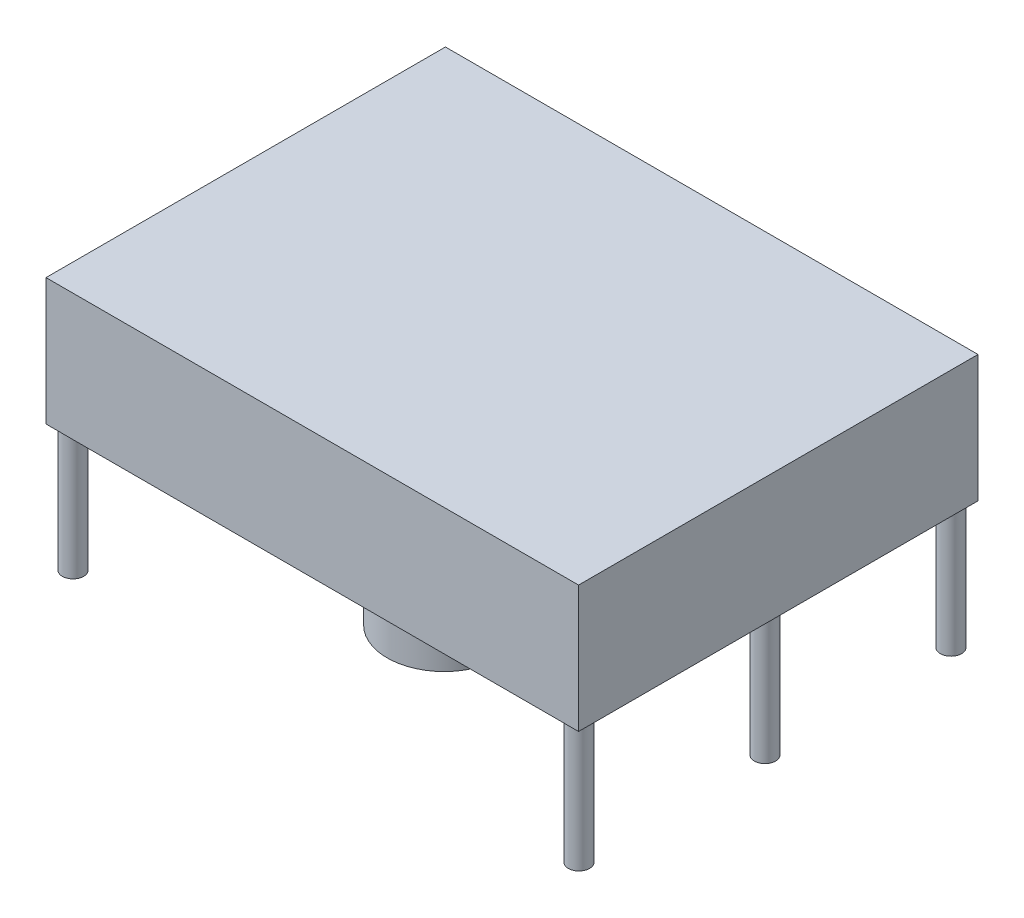
SolidWorks part; units mm, degrees
ref_plane "Front Plane" through (0, 0, 0) normal (0, 0, 1) x (1, 0, 0)
ref_plane "Top Plane" through (0, 0, 0) normal (0, 1, 0) x (1, 0, 0)
ref_plane "Right Plane" through (0, 0, 0) normal (1, 0, 0) x (0, 0, -1)
sketch "Sketch1" plane through (0, 0, 0) normal (0, 1, 0) x (1, 0, 0)
  line L1 (80, 60) -> (-80, 60)
  line L2 (80, 60) -> (80, -60)
  line L3 (80, -60) -> (-80, -60)
  line L4 (-80, 60) -> (-80, -60)
  line L5 (0, -60) -> (0, 60) construction
  line L6 (80, 0) -> (-80, 0) construction
  point P0 (0, 0)
  dimension "D1" = 120
  dimension "D2" = 160
extrude "Boss-Extrude1" add sketch "Sketch1" along normal blind 76.2
sketch "Sketch2" plane through (0, 0, 0) normal (0, -1, 0) x (1, 0, 0)
  line L0 (-76, 55.88) -> (76, 55.88) construction
  line L1 (76, 55.88) -> (76, 0) construction
  line L2 (76, 0) -> (76, -55.88) construction
  line L3 (76, -55.88) -> (-76, -55.88) construction
  line L4 (-76, -55.88) -> (-76, 55.88) construction
  line L5 (0, 0) -> (76, 0) construction
  line L6 (0, 0) -> (-76, 0) construction
  circle A0 centre (-76, 55.88) radius 3.2
  circle A1 centre (76, 55.88) radius 3.2
  circle A2 centre (76, -55.88) radius 3.2
  circle A3 centre (-76, -55.88) radius 3.2
  circle A4 centre (76, 0) radius 3.2
  dimension "D1" = 6.4
  dimension "D2" = 152
  dimension "D3" = 111.76
extrude "Cut-Extrude1" cut sketch "Sketch2" against normal blind 38.1 flip side to cut
sketch "Sketch3" plane through (0, 38.1, 0) normal (0, -1, 0) x (1, 0, 0)
  line L0 (0, -20.375) -> (0, 20.375) construction
  circle A0 centre (0, 20.375) radius 17.125
  circle A1 centre (0, -20.375) radius 17.125
  point P4 (0, 22.1325)
  dimension "D1" = 34.25
  dimension "D2" = 75
extrude "Boss-Extrude2" add sketch "Sketch3" along normal blind 32.12
